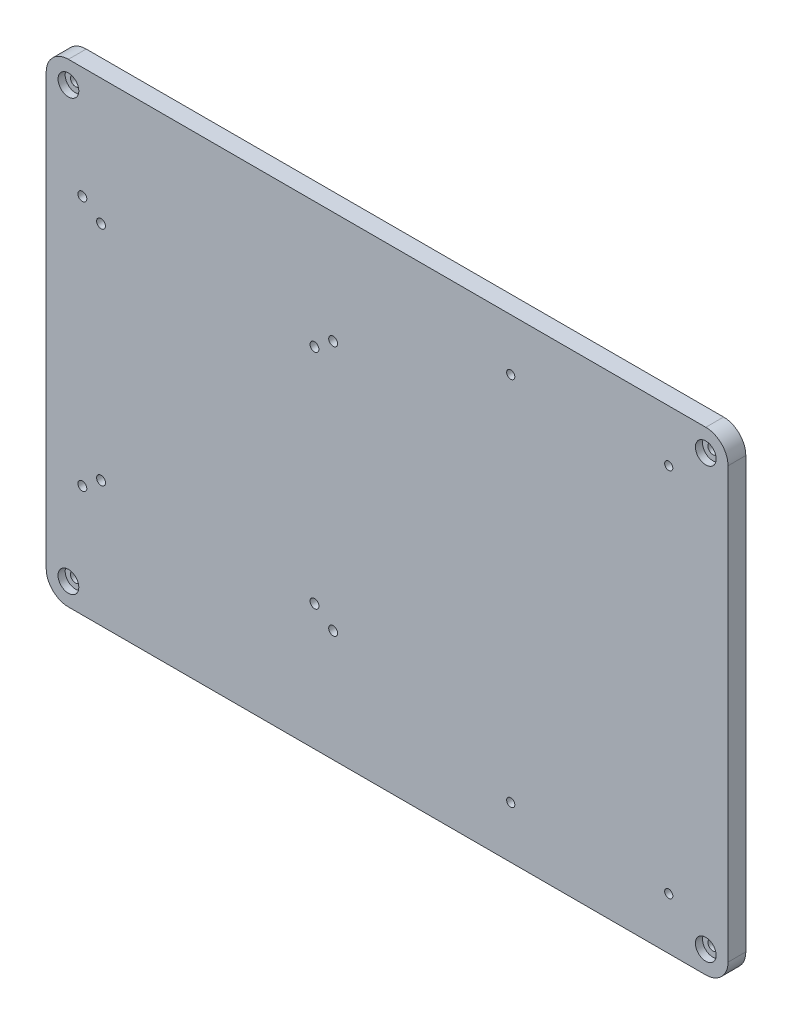
SolidWorks part; units mm, degrees
ref_plane "Front Plane" through (0, 0, 0) normal (0, 0, 1) x (1, 0, 0)
ref_plane "Top Plane" through (0, 0, 0) normal (0, 1, 0) x (1, 0, 0)
ref_plane "Right Plane" through (0, 0, 0) normal (1, 0, 0) x (0, 0, -1)
sketch "Sketch1" plane through (0, 0, 0) normal (0, 0, 1) x (1, 0, 0)
  line L1 (-107.5, 80) -> (107.5, 80)
  line L2 (-115, 72.5) -> (-115, -72.5)
  line L3 (-107.5, -80) -> (107.5, -80)
  line L4 (115, 72.5) -> (115, -72.5)
  line L5 (-115, 80) -> (115, -80) construction
  line L6 (-115, -80) -> (115, 80) construction
  arc A0 (-115, -72.5) -> (-107.5, -80) centre (-107.5, -72.5) ccw
  arc A1 (107.5, -80) -> (115, -72.5) centre (107.5, -72.5) ccw
  arc A2 (107.5, 80) -> (115, 72.5) centre (107.5, 72.5) cw
  arc A3 (-107.5, 80) -> (-115, 72.5) centre (-107.5, 72.5) ccw
  point P0 (0, 0)
  dimension "D3" = 7.5
  dimension "D1" = 230
  dimension "D2" = 160
extrude "Boss-Extrude1" add sketch "Sketch1" along normal blind 6
sketch "Sketch4" plane through (0, 0, 6) normal (0, 0, 1) x (1, 0, 0)
  line L0 (107.5, 80) -> (-107.5, 80) construction
  line L3 (-115, 72.5) -> (-115, -72.5) construction
  line L4 (-107.5, -80) -> (107.5, -80) construction
  circle A0 centre (-96.5, 37.5) radius 1.5
  circle A1 centre (-96.5, -37.5) radius 1.5
  circle A2 centre (-24.5, 37.5) radius 1.5
  circle A3 centre (-24.5, -37.5) radius 1.5
  dimension "D2" = 3
  dimension "D3" = 3
  dimension "D6" = 3
  dimension "D7" = 3
  dimension "D12" = 18.5
  dimension "D1" = 75
  dimension "D4" = 42.5
  dimension "D5" = 18.5
  dimension "D8" = 72
  dimension "D9" = 72
  dimension "D10" = 42.5
  dimension "D11" = 42.5
extrude "Cut-Extrude3" cut sketch "Sketch4" against normal through all
sketch "Sketch5" plane through (0, 0, 6) normal (0, 0, 1) x (1, 0, 0)
  line L0 (-107.5, -80) -> (107.5, -80) construction
  line L1 (107.5, 80) -> (-107.5, 80) construction
  line L2 (115, -72.5) -> (115, 72.5) construction
  circle A0 centre (95, -62.5) radius 1.375
  circle A1 centre (95, 62.5) radius 1.375
  circle A2 centre (41.7, -62.5) radius 1.375
  circle A3 centre (41.7, 62.5) radius 1.375
  dimension "D1" = 125
  dimension "D4" = 2.75
  dimension "D6" = 53.3
  dimension "D7" = 125
  dimension "D8" = 20
  dimension "D9" = 17.5
  dimension "D2" = 17.5
  dimension "D3" = 20
  dimension "D5" = 53.3
extrude "Cut-Extrude4" cut sketch "Sketch5" against normal through all and the other way through all
sketch "Sketch7" plane through (0, 0, 6) normal (0, 0, 1) x (1, 0, 0)
  circle A0 centre (-102.8, 42.3) radius 1.5
  circle A1 centre (-96.5, 37.5) radius 1.5 construction
  circle A2 centre (-102.8, -42.3) radius 1.5
  circle A3 centre (-18.2, -42.3) radius 1.5
  circle A4 centre (-18.2, 42.3) radius 1.5
  circle A5 centre (-96.5, -37.5) radius 1.5 construction
  circle A6 centre (-24.5, -37.5) radius 1.5 construction
  circle A7 centre (-24.5, 37.5) radius 1.5 construction
  dimension "D1" = 6.3
  dimension "D3" = 3
  dimension "D4" = 3
  dimension "D5" = 3
  dimension "D6" = 3
  dimension "D7" = 4.8
  dimension "D8" = 6.3
  dimension "D10" = 4.8
  dimension "D11" = 4.8
  dimension "D12" = 6.3
  dimension "D2" = 4.8
extrude "Cut-Extrude6" cut sketch "Sketch7" against normal through all
sketch "Sketch8" plane through (0, 0, 0) normal (0, 0, -1) x (-1, 0, 0)
  circle A0 centre (18.2, 42.3) radius 3
  circle A1 centre (18.2, -42.3) radius 3
  circle A2 centre (102.8, -42.3) radius 3
  circle A3 centre (102.8, 42.3) radius 3
  dimension "D1" = 6
  dimension "D2" = 6
  dimension "D3" = 6
  dimension "D4" = 6
extrude "Cut-Extrude7" cut sketch "Sketch8" against normal blind 3.5
hole_wizard "CBORE for M3 Pan Head Machine Screw1" positions "Sketch9" profile "Sketch10" counterbore size "M3" standard "ANSI Metric" end condition through all
sketch "Sketch9" plane through (0, 0, 6) normal (0, 0, 1) x (1, 0, 0)
  line L1 (107.5, 80) -> (-107.5, 80) construction
  line L2 (-115, 72.5) -> (-115, -72.5) construction
  line L3 (-107.5, -80) -> (107.5, -80) construction
  line L4 (115, -72.5) -> (115, 72.5) construction
  point P0 (-107.5, 72.5)
  point P2 (-107.5, -72.5)
  point P4 (107.5, -72.5)
  point P6 (107.5, 72.5)
  dimension "D1" = 7.5
  dimension "D2" = 7.5
  dimension "D3" = 7.5
  dimension "D4" = 7.5
  dimension "D5" = 7.5
  dimension "D6" = 7.5
  dimension "D7" = 7.5
  dimension "D8" = 7.5
sketch "Sketch10" plane through (-107.5, 72.5, 6) normal (1, 0, 0) x (0, -1, 0)
  line L0 (0, 0) -> (0, 6)
  line L1 (0, 6) -> (1.7, 6)
  line L3 (1.7, 6) -> (1.7, 2.4)
  line L4 (1.7, 2.4) -> (3.5, 2.4)
  line L5 (3.5, 2.4) -> (3.5, 0)
  line L7 (3.5, 0) -> (0, 0)
  line L11 (0, -6.35) -> (0, 107.95) construction
  dimension "Thru Hole Dia." = 3.4
  dimension "Thru Hole Depth" = 6
  dimension "C'Bore Dia." = 7
  dimension "C'Bore Depth" = 2.4
